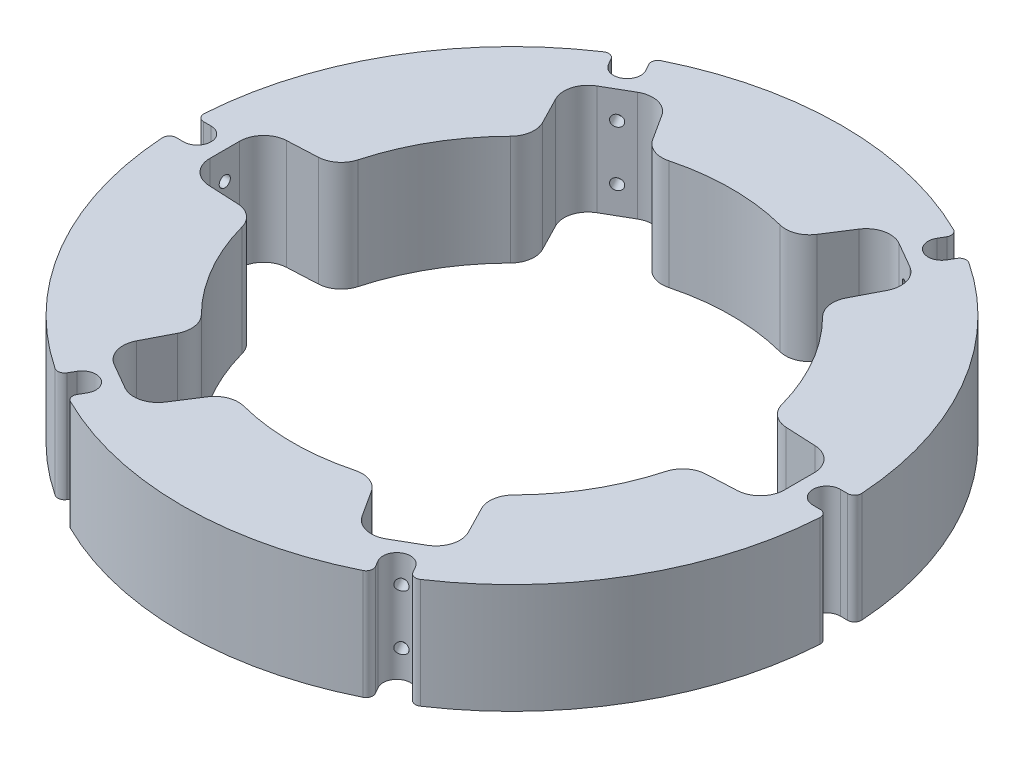
SolidWorks part; units mm, degrees
material "6061-T6 (SS)"
ref_plane "Front Plane" through (0, 0, 0) normal (0, 0, 1) x (1, 0, 0)
ref_plane "Top Plane" through (0, 0, 0) normal (0, 1, 0) x (1, 0, 0)
ref_plane "Right Plane" through (0, 0, 0) normal (1, 0, 0) x (0, 0, -1)
sketch "Sketch1" plane through (0, 0, 0) normal (0, 1, 0) x (1, 0, 0)
  circle A0 centre (0, 0) radius 76.2
  circle A1 centre (0, 0) radius 50.8
  dimension "D1" = 152.4
  dimension "D2" = 101.6
extrude "Boss-Extrude1" add sketch "Sketch1" against normal blind 12.7
sketch "Sketch3" plane through (0, -12.7, 0) normal (0, -1, 0) x (-1, 0, 0)
  line L0 (-76.1338, 3.175) -> (-72.771, 3.175)
  line L1 (-76.1338, -3.175) -> (-72.771, -3.175)
  circle A0 centre (0, 0) radius 76.2 construction
  arc A1 (-72.771, 3.175) -> (-72.771, -3.175) centre (-72.771, 0) cw
  arc A2 (-76.1338, -3.175) -> (-76.1338, 3.175) centre (0, 0) cw
  point P9 (-69.596, 0)
  point P13 (-76.2, 0)
  dimension "D1" = 6.35
  dimension "D2" = 6.604
extrude "Cut-Extrude1" cut sketch "Sketch3" against normal blind 12.7
sketch "Sketch4" plane through (0, -12.7, 0) normal (0, -1, 0) x (-1, 0, 0)
  line L0 (-66.421, 8.7312) -> (-66.421, -8.7312)
  line L1 (-66.421, -8.7312) -> (-49.899, -9.525)
  line L2 (-49.899, -9.525) -> (-49.899, 9.525)
  line L3 (-49.899, 9.525) -> (-66.421, 8.7312)
  line L4 (-66.421, 0) -> (0, 0) construction
  circle A0 centre (0, 0) radius 50.8 construction
  dimension "D1" = 3.175
  dimension "D2" = 19.05
  dimension "D3" = 17.4625
extrude "Cut-Extrude2" cut sketch "Sketch4" against normal through all
hole_wizard "#5-40 Tapped Hole1" positions "Sketch5" profile "Sketch6" tap size "#5-40" standard "ANSI Inch" end condition through all
sketch "Sketch5" plane through (66.421, 0, 0) normal (-1, 0, 0) x (0, 0, 1)
  line L0 (-8.7312, -12.7) -> (8.7312, -12.7) construction
  point P0 (0, -6.35)
  dimension "D1" = 6.35
sketch "Sketch6" plane through (66.421, -6.35, 0) normal (0, 1, 0) x (0, 0, 1)
  line L0 (0, 0) -> (0, 9.7128)
  line L1 (0, 9.7128) -> (1.289, 9.7128)
  line L2 (1.289, 9.7128) -> (1.289, 0)
  line L5 (1.289, 0) -> (0, 0)
  line L11 (0, -6.35) -> (0, 107.95) construction
  dimension "Thru Tap Drill Dia." = 2.5781
  dimension "Thru Tap Drill Depth" = 9.7128
cosmetic thread "Hole Thread1" parameters "D2"=3.175
fillet "Fillet1" radius 1.5875 2 edges at (76.1338, -6.35, 3.175) (76.1338, -6.35, -3.175)
fillet "Fillet2" radius 5.5562 4 edges at (66.421, -6.35, 8.7312) (66.421, -6.35, -8.7312) (49.899, -6.35, 9.525) (49.899, -6.35, -9.525)
pattern_circular "CirPattern1" count 6 over 360 about axis through (0, -12.7, 0) along (0, 1, 0) of "Cut-Extrude1", "Cut-Extrude2", "Fillet2", "Fillet1", "#5-40 Tapped Hole1"
cosmetic thread "Hole Thread2" parameters "D2"=3.175
cosmetic thread "Hole Thread3" parameters "D2"=3.175
cosmetic thread "Hole Thread4" parameters "D2"=3.175
cosmetic thread "Hole Thread5" parameters "D2"=3.175
cosmetic thread "Hole Thread6" parameters "D2"=3.175
mirror "Mirror3" about plane through (0, 0, 0) normal (0, 1, 0) of bodies 103
cosmetic thread "Hole Thread8" parameters "D2"=3.175
cosmetic thread "Hole Thread9" parameters "D2"=3.175
cosmetic thread "Hole Thread10" parameters "D2"=3.175
cosmetic thread "Hole Thread11" parameters "D2"=3.175
cosmetic thread "Hole Thread12" parameters "D2"=3.175
cosmetic thread "Hole Thread13" parameters "D2"=3.175
